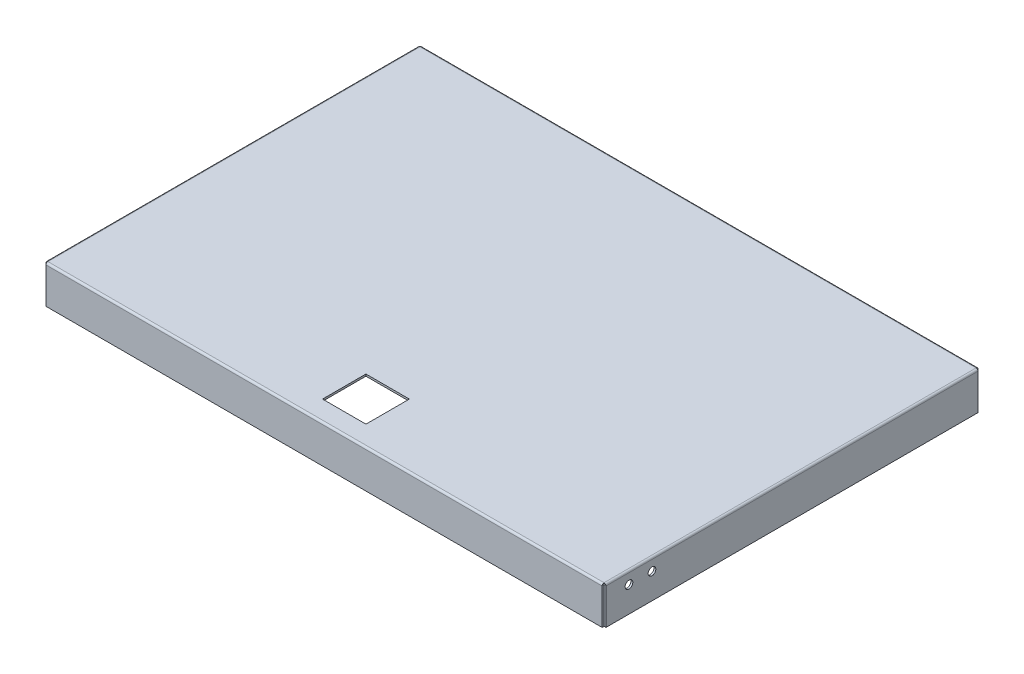
SolidWorks part; units mm, degrees
material "Acrylic (Medium-high impact)"
ref_plane "Front Plane" through (0, 0, 0) normal (0, 0, 1) x (1, 0, 0)
ref_plane "Top Plane" through (0, 0, 0) normal (0, 1, 0) x (1, 0, 0)
ref_plane "Right Plane" through (0, 0, 0) normal (1, 0, 0) x (0, 0, -1)
sketch "Sketch1" plane through (0, 0, 0) normal (0, 1, 0) x (1, 0, 0)
  line L0 (-3.175, -3.175) -> (-3.175, 619.125)
  line L1 (0, 0) -> (920.75, 0)
  line L2 (0, 0) -> (0, 615.95)
  line L3 (0, 615.95) -> (920.75, 615.95)
  line L4 (920.75, 0) -> (920.75, 615.95)
  line L5 (-3.175, 619.125) -> (923.925, 619.125)
  line L6 (923.925, -3.175) -> (923.925, 619.125)
  line L7 (-3.175, -3.175) -> (923.925, -3.175)
  line L8 (3.175, 3.175) -> (3.175, 612.775)
  line L9 (3.175, 612.775) -> (917.575, 612.775)
  line L10 (917.575, 3.175) -> (917.575, 612.775)
  line L11 (3.175, 3.175) -> (917.575, 3.175)
  line L13 (-3.175, 619.125) -> (0, 619.125)
  line L14 (-3.175, 619.125) -> (-3.175, 615.95)
  line L15 (-3.175, 615.95) -> (0, 615.95)
  line L16 (0, 619.125) -> (0, 615.95)
  line L17 (0, 0) -> (-3.175, 0)
  line L18 (0, 0) -> (0, -3.175)
  line L19 (0, -3.175) -> (-3.175, -3.175)
  line L20 (-3.175, 0) -> (-3.175, -3.175)
  line L21 (923.925, -3.175) -> (920.75, -3.175)
  line L22 (923.925, -3.175) -> (923.925, 0)
  line L23 (923.925, 0) -> (920.75, 0)
  line L24 (920.75, -3.175) -> (920.75, 0)
  line L25 (923.925, 619.125) -> (920.75, 619.125)
  line L26 (923.925, 619.125) -> (923.925, 615.95)
  line L27 (923.925, 615.95) -> (920.75, 615.95)
  line L28 (920.75, 619.125) -> (920.75, 615.95)
  dimension "D2" = 3.175
  dimension "D3" = 609.6
  dimension "D4" = 914.4
  dimension "D1" = 3.175
extrude "Skirt" add sketch "Sketch1" along normal blind 59.4 contours L0 L7 L6 L5 L4 L1 L2 L3 | L17 L2 L15 L0 | L28 L5 L16 L3 | L6 L27 L4 L23 region at (-1.5875, 0, -307.975) region at (460.375, 0, 1.5875) region at (460.375, 0, -617.5375) region at (922.3375, 0, -307.975)
sketch "Sketch2" plane through (0, 59.4, 0) normal (0, 1, 0) x (1, 0, 0)
  line L0 (-3.175, 0) -> (0, 0)
  line L1 (0, -3.175) -> (920.75, -3.175)
  line L2 (-3.175, 0) -> (-3.175, 615.95)
  line L3 (0, 619.125) -> (920.75, 619.125)
  line L4 (923.925, 0) -> (923.925, 615.95)
  line L5 (0, 0) -> (0, -3.175)
  line L6 (-3.175, 615.95) -> (0, 615.95)
  line L7 (0, 615.95) -> (0, 619.125)
  line L8 (0, 619.125) -> (0, 615.95) construction
  line L11 (920.75, 619.125) -> (920.75, 615.95)
  line L12 (920.75, 615.95) -> (923.925, 615.95)
  line L15 (920.75, -3.175) -> (920.75, 0)
  line L16 (920.75, 0) -> (923.925, 0)
extrude "Top Surface" add sketch "Sketch2" along normal blind 3.175
fillet "Fillet1" radius 3.175 4 edges at (923.925, 62.575, -307.975) (460.375, 62.575, -619.125) (460.375, 62.575, 3.175) (-3.175, 62.575, -307.975)
sketch "Sketch3" plane through (0, 62.575, 0) normal (0, 1, 0) x (1, 0, 0)
  line L0 (425.45, 31.242) -> (495.3, 101.092) construction
  line L1 (425.45, 31.242) -> (495.3, 31.242) construction
  line L2 (425.45, 31.242) -> (425.45, 101.092) construction
  line L3 (425.45, 101.092) -> (495.3, 101.092) construction
  line L4 (495.3, 31.242) -> (495.3, 101.092) construction
  line L5 (460.375, 66.167) -> (460.375, -3.175) construction
  line L6 (0, -3.175) -> (920.75, -3.175) construction
  line L7 (0, -3.175) -> (920.75, -3.175) construction
  line L8 (424.434, 102.108) -> (496.316, 102.108)
  line L9 (496.316, 30.226) -> (496.316, 102.108)
  line L10 (424.434, 30.226) -> (496.316, 30.226)
  line L11 (424.434, 30.226) -> (424.434, 102.108)
  point P10 (460.375, -3.175)
  dimension "D1" = 69.342
  dimension "D2" = 69.85
  dimension "D3" = 1.016
extrude "Scale Hole" cut sketch "Sketch3" against normal through all both and the other way through all
sketch "Sketch4" plane through (923.925, 0, 0) normal (1, 0, 0) x (0, 0, -1)
  line L1 (38.1, 42.4) -> (0, 42.4) construction
  line L5 (38.1, 42.4) -> (76.2, 42.4) construction
  line L6 (0, 59.4) -> (0, 0) construction
  line L7 (0, 0) -> (25.4, 0) construction
  line L8 (0, 0) -> (0, 25.4) construction
  line L9 (0, 25.4) -> (25.4, 25.4) construction
  line L10 (25.4, 0) -> (25.4, 25.4) construction
  line L11 (12.7, 25.4) -> (12.7, 59.4) construction
  line L12 (0, 59.4) -> (615.95, 59.4) construction
  circle A0 centre (38.1, 42.4) radius 6.35
  circle A1 centre (76.2, 42.4) radius 6.35
  point P10 (12.7, 42.4)
  point P18 (58.6424, 42.4)
  dimension "D1" = 12.7
  dimension "D2" = 25.4
  dimension "D3" = 38.1
extrude "Tether and Air Hole" cut sketch "Sketch4" against normal up to surface (3.175 mm away) up to face at (920.75, 29.7, -307.975)
